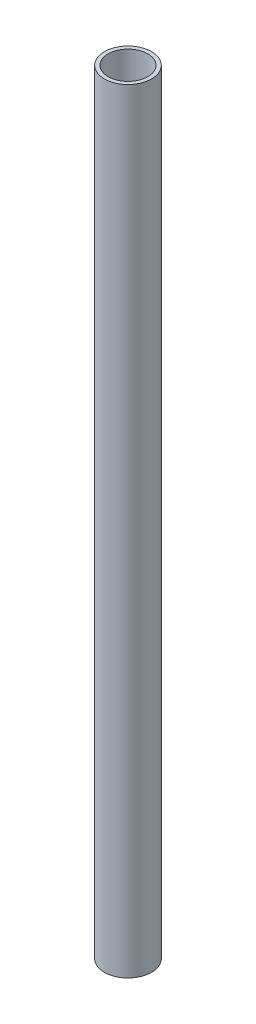
SolidWorks part; units mm, degrees
material "Hexcel AS4C (3000 Filaments)"
ref_plane "Front Plane" through (0, 0, 0) normal (0, 0, 1) x (1, 0, 0)
ref_plane "Top Plane" through (0, 0, 0) normal (0, 1, 0) x (1, 0, 0)
ref_plane "Right Plane" through (0, 0, 0) normal (1, 0, 0) x (0, 0, -1)
sketch "Sketch1" plane through (0, 0, 0) normal (0, 1, 0) x (1, 0, 0)
  circle A0 centre (0, 0) radius 12.5
  circle A1 centre (0, 0) radius 10.5
  dimension "D1" = 25
  dimension "D2" = 21
extrude "Boss-Extrude1" add sketch "Sketch1" along normal blind 205 and the other way blind 205
